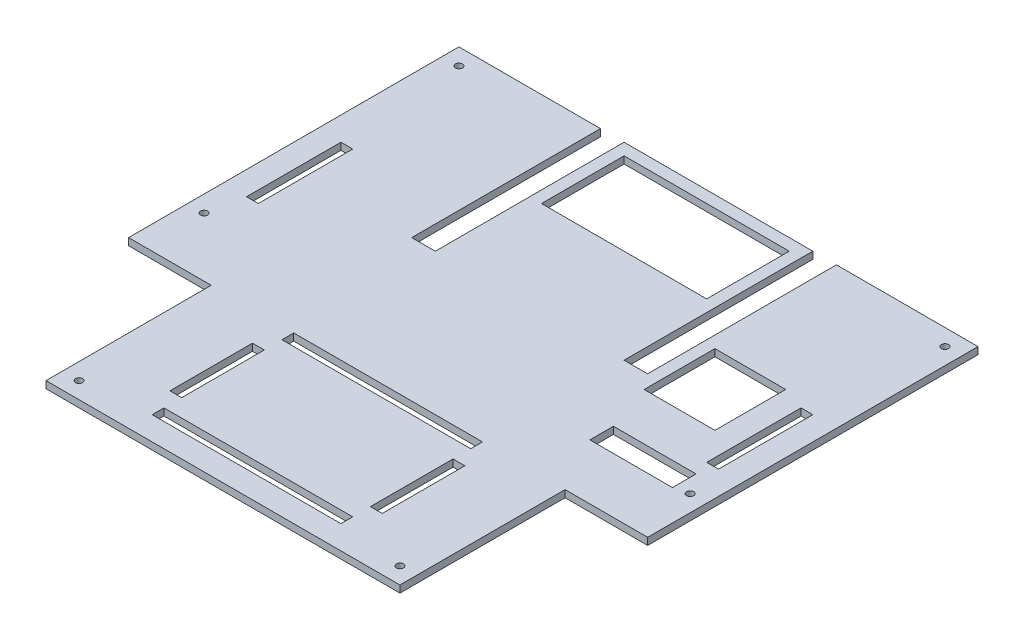
SolidWorks part; units mm, degrees
material "Pine"
ref_plane "Front Plane" through (0, 0, 0) normal (0, 0, 1) x (1, 0, 0)
ref_plane "Top Plane" through (0, 0, 0) normal (0, 1, 0) x (1, 0, 0)
ref_plane "Right Plane" through (0, 0, 0) normal (1, 0, 0) x (0, 0, -1)
sketch "Sketch4" plane through (0, 0, 0) normal (0, 1, 0) x (1, 0, 0)
  line L1 (0, 0) -> (-220, 0)
  line L2 (0, 0) -> (0, 210)
  line L3 (0, 210) -> (-220, 210)
  line L4 (-220, 0) -> (-220, 210)
  dimension "D1" = 220
  dimension "D2" = 210
extrude "Boss-Extrude1" add sketch "Sketch4" along normal blind 3
sketch "Sketch5" plane through (0, 3, 0) normal (0, 1, 0) x (1, 0, 0)
  line L1 (-220, 0) -> (-185, 0)
  line L2 (-220, 0) -> (-220, 70)
  line L3 (-220, 70) -> (-185, 70)
  line L4 (-185, 0) -> (-185, 70)
  dimension "D1" = 35
  dimension "D2" = 70
extrude "Cut-Extrude1" cut sketch "Sketch5" against normal blind 3
sketch "Sketch6" plane through (0, 3, 0) normal (0, 1, 0) x (1, 0, 0)
  line L1 (0, 0) -> (-35, 0)
  line L2 (0, 0) -> (0, 70)
  line L3 (0, 70) -> (-35, 70)
  line L4 (-35, 0) -> (-35, 70)
  dimension "D1" = 35
  dimension "D2" = 70
extrude "Cut-Extrude2" cut sketch "Sketch6" against normal blind 3
sketch "Sketch12" plane through (0, 3, 0) normal (0, 1, 0) x (1, 0, 0)
  line L2 (-35, 88) -> (-35, 80)
  line L5 (-35, 70) -> (-35, 0) construction
  dimension "D4" = 0
extrude "Cut-Extrude8" cut sketch "Sketch12" against normal blind 3 rebuild error yes
sketch "Sketch13" plane through (0, 3, 0) normal (0, 1, 0) x (1, 0, 0)
  line L4 (-215, 80) -> (-215, 88)
  dimension "D1" = 8
extrude "Cut-Extrude9" cut sketch "Sketch13" against normal blind 3 rebuild error yes
sketch "Sketch14" plane through (0, 3, 0) normal (0, 1, 0) x (1, 0, 0)
  line L0 (-110, 210) -> (-110, 0)
  line L1 (0, 210) -> (-220, 210) construction
  line L2 (-185, 0) -> (-35, 0) construction
sketch "Sketch22" plane through (0, 3, 0) normal (0, 1, 0) x (1, 0, 0)
  line L0 (-185, 0) -> (-185, 70) construction
  line L1 (-185, 0) -> (-35, 0) construction
  circle A0 centre (-178, 7) radius 1.5
  dimension "D1" = 7
  dimension "D2" = 7
sketch "Sketch24" plane through (0, 3, 0) normal (0, 1, 0) x (1, 0, 0)
  line L2 (-185, 0) -> (-35, 0) construction
  line L3 (-35, 70) -> (-35, 0) construction
  circle A0 centre (-42, 7) radius 1.5
  dimension "D1" = 7
  dimension "D2" = 7
sketch "Sketch25" plane through (0, 3, 0) normal (0, 1, 0) x (1, 0, 0)
  line L2 (0, 210) -> (-220, 210) construction
  line L3 (0, 70) -> (0, 210) construction
  circle A0 centre (-7, 203) radius 1.5
  dimension "D1" = 7
  dimension "D2" = 7
sketch "Sketch26" plane through (0, 3, 0) normal (0, 1, 0) x (1, 0, 0)
  line L2 (0, 210) -> (-220, 210) construction
  line L3 (-220, 210) -> (-220, 70) construction
  circle A0 centre (-213, 203) radius 1.5
  dimension "D1" = 7
  dimension "D2" = 7
extrude "Cut-Extrude15" cut sketch "Sketch22" against normal blind 3
extrude "Cut-Extrude16" cut sketch "Sketch26" against normal blind 3 contours A0
extrude "Cut-Extrude17" cut sketch "Sketch24" against normal blind 3
extrude "Cut-Extrude18" cut sketch "Sketch25" against normal blind 3
sketch "Sketch27" plane through (0, 3, 0) normal (0, 1, 0) x (1, 0, 0)
  line L0 (-220, 210) -> (-220, 70) construction
  line L1 (-185, 88) -> (-215, 88) construction
  circle A0 centre (-213, 95) radius 1.5
  dimension "D1" = 7
  dimension "D2" = 7
extrude "Cut-Extrude19" cut sketch "Sketch27" against normal blind 3
sketch "Sketch28" plane through (0, 3, 0) normal (0, 1, 0) x (1, 0, 0)
  line L0 (-5, 88) -> (-35, 88) construction
  line L1 (0, 70) -> (0, 210) construction
  circle A0 centre (-7, 95) radius 1.5
  dimension "D1" = 7
  dimension "D2" = 7
extrude "Cut-Extrude20" cut sketch "Sketch28" against normal blind 3
sketch "Sketch55" plane through (0, 3, 0) normal (0, 1, 0) x (1, 0, 0)
  line L1 (-52.038, 199.3694) -> (-7.038, 199.3694)
  line L2 (-52.038, 199.3694) -> (-52.038, 174.3694)
  line L3 (-52.038, 174.3694) -> (-7.038, 174.3694)
  line L4 (-7.038, 199.3694) -> (-7.038, 174.3694)
  dimension "D1" = 45
  dimension "D2" = 25
sketch "Sketch56" plane through (0, 3, 0) normal (0, 1, 0) x (1, 0, 0)
  line L0 (0, 210) -> (-220, 210) construction
  line L1 (-70, 210) -> (-60, 210)
  line L2 (-70, 210) -> (-70, 130)
  line L3 (-70, 130) -> (-60, 130)
  line L4 (-60, 210) -> (-60, 130)
  line L5 (0, 210) -> (-220, 210) construction
  line L6 (-110, 210) -> (-110, 0)
  line L7 (-185, 0) -> (-35, 0) construction
  line L8 (-150, 130) -> (-160, 130)
  line L9 (-150, 210) -> (-150, 130)
  line L10 (-150, 210) -> (-160, 210)
  line L11 (-160, 210) -> (-160, 130)
  line L13 (-145, 205) -> (-75, 205)
  line L14 (-145, 205) -> (-145, 170)
  line L15 (-145, 170) -> (-75, 170)
  line L16 (-75, 205) -> (-75, 170)
  point P6 (-110, 210)
  line M10 (0, 210) -> (-220, 210)
  dimension "D1" = 40
  dimension "D2" = 10
  dimension "D3" = 80
  dimension "D4" = 70
  dimension "D5" = 35
  dimension "D6" = 5
  dimension "D7" = 35
extrude "Cut-Extrude21" cut sketch "Sketch56" against normal blind 3 contours L14 L15 L6 L13 | L16 L13 L6 L15 | L11 L8 L9 M10 | L2 L3 L4 L1 region at (-92.5, 3, -187.5) region at (-127.5, 3, -187.5) region at (-155, 3, -170)
sketch "Sketch57" plane through (0, 3, 0) normal (0, 1, 0) x (1, 0, 0)
  line L0 (-185, 0) -> (-35, 0) construction
  line L1 (-150, 70) -> (-70, 70)
  line L2 (-150, 70) -> (-150, 65)
  line L3 (-150, 65) -> (-70, 65)
  line L4 (-70, 70) -> (-70, 65)
  line L5 (-185, 70) -> (-220, 70) construction
  line L6 (-150, 15) -> (-70, 15)
  line L7 (-150, 15) -> (-150, 10)
  line L8 (-150, 10) -> (-70, 10)
  line L9 (-70, 15) -> (-70, 10)
  line L10 (-70, 57.5) -> (-65, 57.5)
  line L11 (-70, 57.5) -> (-70, 22.5)
  line L12 (-70, 22.5) -> (-65, 22.5)
  line L13 (-65, 57.5) -> (-65, 22.5)
  line L14 (-150, 57.5) -> (-155, 57.5)
  line L15 (-150, 57.5) -> (-150, 22.5)
  line L16 (-150, 22.5) -> (-155, 22.5)
  line L17 (-155, 57.5) -> (-155, 22.5)
  line L18 (-15, 150) -> (-10, 150)
  line L19 (-15, 150) -> (-15, 110)
  line L20 (-15, 110) -> (-10, 110)
  line L21 (-10, 150) -> (-10, 110)
  line L22 (-210, 150) -> (-205, 150)
  line L23 (-210, 150) -> (-210, 110)
  line L24 (-210, 110) -> (-205, 110)
  line L25 (-205, 150) -> (-205, 110)
  line L26 (-220, 210) -> (-220, 70) construction
  line L27 (0, 70) -> (0, 210) construction
  line L28 (0, 70) -> (-35, 70) construction
  line L30 (-13, 93.5) -> (-48, 93.5)
  line L31 (-13, 93.5) -> (-13, 103.5)
  line L32 (-13, 103.5) -> (-48, 103.5)
  line L33 (-48, 93.5) -> (-48, 103.5)
  line L34 (-55, 153.5) -> (-25, 153.5)
  line L35 (-55, 153.5) -> (-55, 123.5)
  line L36 (-55, 123.5) -> (-25, 123.5)
  line L37 (-25, 153.5) -> (-25, 123.5)
  circle A0 centre (-7, 95) radius 1.5 construction
  point P4 (-110, 0)
  dimension "D23" = 6
  dimension "D25" = 23.5
  dimension "D1" = 80
  dimension "D2" = 40
  dimension "D3" = 5
  dimension "D4" = 10
  dimension "D5" = 5
  dimension "D6" = 5
  dimension "D7" = 5
  dimension "D8" = 35
  dimension "D9" = 35
  dimension "D10" = 7.5
  dimension "D11" = 7.5
  dimension "D12" = 40
  dimension "D13" = 5
  dimension "D14" = 5
  dimension "D15" = 40
  dimension "D16" = 40
  dimension "D17" = 10
  dimension "D18" = 10
  dimension "D19" = 40
  dimension "D20" = 0
  dimension "D21" = 35
  dimension "D22" = 10
  dimension "D24" = 30
  dimension "D26" = 30
  dimension "D27" = 20
  dimension "D28" = 12
extrude "Cut-Extrude22" cut sketch "Sketch57" against normal blind 3
